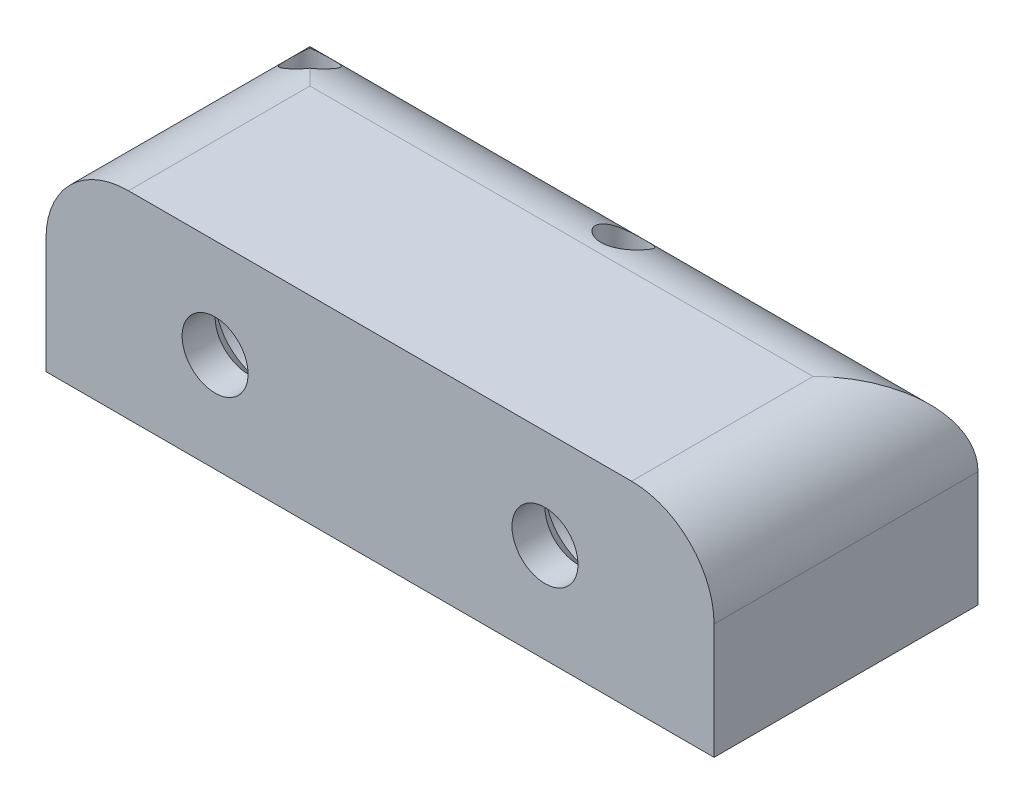
SolidWorks part; units mm, degrees
ref_plane "Front Plane" through (0, 0, 0) normal (0, 0, 1) x (1, 0, 0)
ref_plane "Top Plane" through (0, 0, 0) normal (0, 1, 0) x (1, 0, 0)
ref_plane "Right Plane" through (0, 0, 0) normal (1, 0, 0) x (0, 0, -1)
sketch "Sketch1" plane through (0, 0, 0) normal (0, 1, 0) x (1, 0, 0)
  line L0 (-20.25, 5) -> (20.25, 5) construction
  line L1 (-20.25, -8) -> (20.25, -8)
  line L2 (-20.25, -8) -> (-20.25, 8)
  line L3 (-20.25, 8) -> (20.25, 8)
  line L4 (20.25, -8) -> (20.25, 8)
  line L5 (-20.25, -8) -> (20.25, 8) construction
  line L6 (-20.25, 8) -> (20.25, -8) construction
  line L8 (-18.25, -6) -> (18.25, -6)
  line L9 (-18.25, -6) -> (-18.25, 6)
  line L10 (-18.25, 6) -> (18.25, 6)
  line L11 (18.25, -6) -> (18.25, 6)
  line L12 (-18.25, -6) -> (18.25, 6) construction
  line L13 (-18.25, 6) -> (18.25, -6) construction
  circle A0 centre (-17.25, 5) radius 1.35
  circle A1 centre (1.75, 5) radius 1.35
  circle A2 centre (-17.25, 5) radius 3
  circle A3 centre (1.75, 5) radius 3
  point P0 (0, 0)
  point P12 (0, 0)
  dimension "D4" = 2.7
  dimension "D5" = 2.7
  dimension "D1" = 40.5
  dimension "D2" = 16
  dimension "D3" = 3
  dimension "D6" = 3
  dimension "D7" = 19
  dimension "D8" = 2
  dimension "D9" = 2
extrude "Boss-Extrude1" add sketch "Sketch1" along normal blind 12 contours A3 L10 L11 L8 L9 A2 L2 L1 L4 L3 | L9 A2 L10 A0 | A3 L3 A2 L10 | L10 A2 L9 A0 | A2 L3 L2 | L10 A3 A1 | L10 A3 A1 | A0 L10 L9 region at (-19.8145, 0, 1.5) region at (-19.5799, 0, -7.3299) region at (-19.313, 0, -7.063) region at (-7.75, 0, -7.0476) region at (-16.0537, 0, -3.8037) region at (1.75, 0, -6.8667) region at (4.6357, 0, -5.4951) region at (-18.2195, 0, -5.9695)
extrude "Boss-Extrude2" add sketch "Sketch1<3>" along normal blind 10 from offset 2 contours A3 L10 A2 L9 L8 L11 region at (0.481, 0, 0.355)
sketch "Sketch1<3>" plane through (0, 0, 0) normal (0, 1, 0) x (1, 0, 0) same geometry as "Sketch1"
sketch "Sketch2" plane through (0, 0, -8) normal (0, 0, -1) x (-1, 0, 0)
  line L0 (20.25, 6) -> (-20.25, 6) construction
  line L1 (20.25, 12) -> (20.25, 0) construction
  line L2 (-20.25, 12) -> (-20.25, 0) construction
  line L3 (0, 0) -> (0, 7.7577) construction
  line L4 (20.25, 0) -> (-20.25, 0) construction
  circle A0 centre (10, 6) radius 3.5
  circle A1 centre (-10, 6) radius 3.5
  circle A2 centre (10, 6) radius 2
  circle A3 centre (-10, 6) radius 2
  dimension "D1" = 10
  dimension "D2" = 7
  dimension "D3" = 4
  dimension "D4" = 4
extrude "Cut-Extrude1" cut sketch "Sketch2" against normal blind 13 contours A2 | A3 | A1 A3 | A0 A2 region at (-6.599, 6, -8) region at (13.401, 6, -8) region at (-10, 6, -8) region at (10, 6, -8)
extrude "Cut-Extrude2" cut sketch "Sketch2<3>" against normal through all contours A3 | A2 region at (-10, 6, -8) region at (10, 6, -8)
sketch "Sketch2<3>" plane through (0, 0, -8) normal (0, 0, -1) x (-1, 0, 0) same geometry as "Sketch2"
chamfer "Chamfer1" distance 1 angle 45 2 edges at (8, 6, 5) (-12, 6, 5)
fillet "Fillet1" radius 5 3 edges at (0, 12, -8) (20.25, 12, 0) (-20.25, 12, 0)
